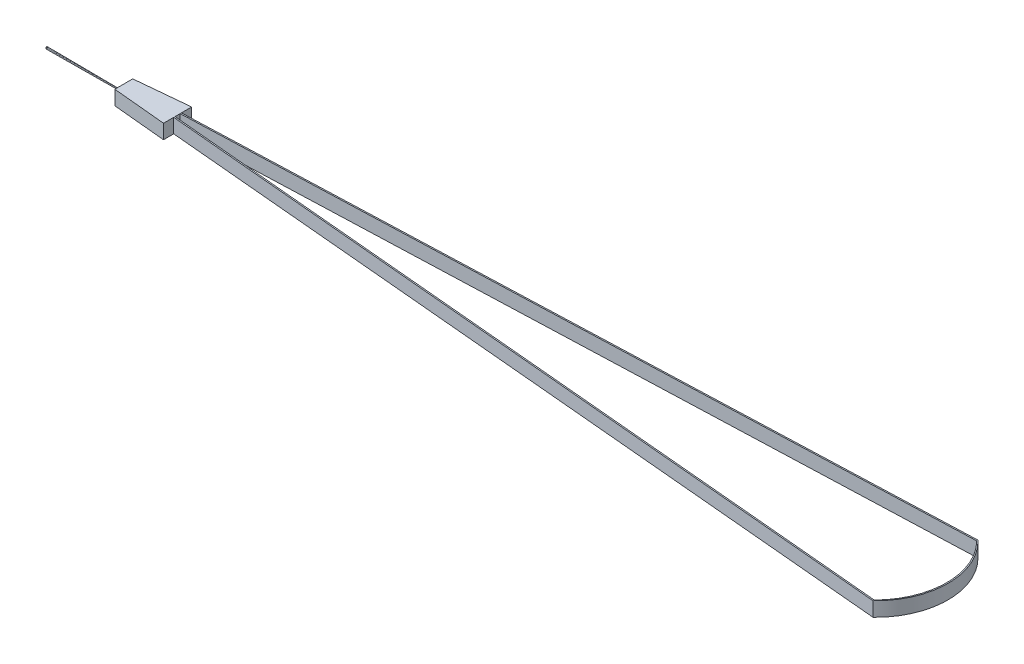
SolidWorks part; units mm, degrees
material "Nylon 101"
ref_plane "Front Plane" through (0, 0, 0) normal (0, 0, 1) x (1, 0, 0)
ref_plane "Top Plane" through (0, 0, 0) normal (0, 1, 0) x (1, 0, 0)
ref_plane "Right Plane" through (0, 0, 0) normal (1, 0, 0) x (0, 0, -1)
sketch "Sketch1" plane through (0, 0, 0) normal (0, 1, 0) x (1, 0, 0)
  line L0 (-10.0935, 6.5032) -> (10.9065, 8.5032)
  line L2 (-10.0935, 6.5032) -> (-10.0935, -0.4968)
  line L5 (10.9065, 8.5032) -> (10.9065, -2.4968)
  line L6 (10.9065, -2.4968) -> (-10.0935, -0.4968)
  point P8 (10.9065, 8.5032)
  point P9 (10.9065, -2.4968)
  dimension "D2" = 7
extrude "Boss-Extrude1" add sketch "Sketch1" along normal blind 5.6
sketch "Sketch2" plane through (-10.0935, 0, 0) normal (-1, 0, 0) x (0, 0, 1)
  line L0 (-6.5032, 5.6) -> (-6.5032, 0) construction
  line L2 (-6.5032, 5.6) -> (0.4968, 5.6) construction
  line L5 (-2.7532, 2.55) -> (-3.2532, 2.55)
  line L6 (-2.7532, 2.55) -> (-2.7532, 3.05)
  line L7 (-2.7532, 3.05) -> (-3.2532, 3.05)
  line L8 (-3.2532, 2.55) -> (-3.2532, 3.05)
  line L9 (-2.7532, 2.55) -> (-3.2532, 3.05) construction
  line L10 (-2.7532, 3.05) -> (-3.2532, 2.55) construction
  point P0 (-3.0032, 2.8)
  point P7 (-3.0032, 2.8)
  dimension "D1" = 3.5
  dimension "D2" = 2.8
  dimension "D3" = 0.5
  dimension "D4" = 0.5
extrude "Boss-Extrude2" add sketch "Sketch2" along normal blind 100 contours L6 L7 L8 L5
sketch "Sketch3" plane through (0, 3.05, 0) normal (0, 1, 0) x (1, 0, 0)
  line L0 (-10.0935, 2.7532) -> (-10.0935, 3.2532) construction
  line L1 (-10.0935, 3.2532) -> (-40.0935, 3.2532)
  line L2 (-110.0935, 3.2532) -> (-10.0935, 3.2532) construction
  line L3 (-40.0935, 3.2532) -> (-40.0935, 2.7532)
  line L4 (-110.0935, 2.7532) -> (-10.0935, 2.7532) construction
  line L5 (-40.0935, 2.7532) -> (-10.0935, 3.0032)
  line L6 (-10.0935, 3.0032) -> (-40.0935, 3.2532)
  line L7 (-40.0935, 3.2532) -> (-40.0935, 3.2782)
  line L8 (-40.0935, 2.7532) -> (-40.0935, 2.7282)
  line L9 (-40.0935, 3.2782) -> (-10.0935, 3.0282)
  line L10 (-10.0935, 3.0032) -> (-10.0935, 3.0282)
  line L11 (-40.0935, 2.7282) -> (-10.0935, 2.9782)
  arc A0 (-40.0935, 3.2532) -> (-40.0935, 2.7532) centre (-40.0703, 3.0032) ccw
  arc A1 (-40.0935, 3.2782) -> (-40.0935, 2.7282) centre (-40.0704, 3.0032) ccw
  point P0 (-10.0935, 3.0032)
  point P16 (-40.3464, 3.0032)
  point P17 (-40.3214, 3.0032)
  line M7 (-10.0935, 2.7532) -> (-10.0935, 3.2532)
  line M8 (-10.0935, 3.2532) -> (-110.0935, 3.2532)
  line M9 (-110.0935, 3.2532) -> (-110.0935, 2.7532)
  line M10 (-110.0935, 2.7532) -> (-10.0935, 2.7532)
  dimension "D1" = 30
  dimension "D2" = 0.025
  dimension "D3" = 0.025
  dimension "D4" = 0.025
  dimension "D5" = 0.025
  dimension "D6" = 0.025
extrude "Cut-Extrude1" cut sketch "Sketch3" against normal blind 100 contours A1 M8 M9 M10 | L3 A0 | L5 L6 L3 | L9 M8 M7 | L11 M10 M7 region at (-19.0935, 3.05, -3.1782) region at (-30.0935, 3.05, -3.0032) region at (-40.1895, 3.05, -3.0032) region at (-75.1975, 3.05, -3.0032) region at (-19.0935, 3.05, -2.8282)
sketch "Sketch4" plane through (10.9065, 0, 0) normal (1, 0, 0) x (0, 0, -1)
  line L0 (-2.4968, 5.6) -> (8.5032, 5.6) construction
  line L1 (2.0032, 5.6) -> (4.0032, 5.6)
  line L2 (2.0032, 5.6) -> (2.0032, 0)
  line L3 (2.0032, 0) -> (4.0032, 0)
  line L4 (4.0032, 5.6) -> (4.0032, 0)
  line L6 (-2.4968, 5.6) -> (-2.4968, 0) construction
  line L7 (8.5032, 5.6) -> (8.5032, 0) construction
  dimension "D1" = 4.5
  dimension "D2" = 4.5
extrude "Boss-Extrude3" add sketch "Sketch4" along normal blind 300
sketch "Sketch5" plane through (0, 5.6, 0) normal (0, 1, 0) x (1, 0, 0)
  line L0 (10.9065, 4.0032) -> (310.9065, 15.0446)
  line L2 (310.9065, -24.9554) -> (10.9065, 2.0032)
  line L3 (10.9065, 4.5032) -> (310.9065, 15.5446)
  line L4 (10.9065, 4.0032) -> (10.9065, 8.5032) construction
  line L5 (10.9065, 4.0032) -> (10.9065, 4.5032)
  line L6 (10.9065, 2.0032) -> (10.9065, 1.5011)
  line L7 (10.9065, -2.4968) -> (10.9065, 2.0032) construction
  line L8 (10.9065, 1.5011) -> (310.9065, -25.4554)
  line L9 (10.9065, 4.0032) -> (310.9065, 4.0032)
  line L10 (10.9065, 4.0032) -> (10.9065, 2.0032)
  line L11 (10.9065, 2.0032) -> (310.9065, 2.0032)
  line L12 (310.9065, 4.0032) -> (310.9065, 2.0032)
  arc A0 (310.9065, 15.0446) -> (310.9065, -24.9554) centre (290.9065, -4.9554) cw
  arc A1 (310.9065, -25.4554) -> (310.9065, 15.5446) centre (291.378, -4.9554) ccw
  point P16 (319.1907, -4.9554)
  point P17 (319.6907, -4.9554)
  point P18 (0, 0)
  line M4 (10.9065, -2.4968) -> (10.9065, 2.0032)
  line M5 (10.9065, 2.0032) -> (310.9065, 2.0032)
  line M6 (310.9065, 2.0032) -> (310.9065, 4.0032)
  line M7 (310.9065, 4.0032) -> (10.9065, 4.0032)
  line M8 (10.9065, 4.0032) -> (10.9065, 8.5032)
  dimension "D1" = 40
  dimension "D2" = 0.5
  dimension "D3" = 0.5
  dimension "D4" = 0.5
  dimension "D5" = 0.5
extrude "Cut-Extrude4" cut sketch "Sketch5" against normal blind 65 contours L10 M7 M5 M6 region at (160.9065, 5.6, -3.0032)
extrude "Boss-Extrude4" add sketch "Sketch5<8>" against normal blind 5.6 separate body contours L8 A1 L3 L0 A0 L2 M8 M4 region at (14.0214, 5.6, -4.2532)
sketch "Sketch5<8>" plane through (0, 5.6, 0) normal (0, 1, 0) x (1, 0, 0) same geometry as "Sketch5"
